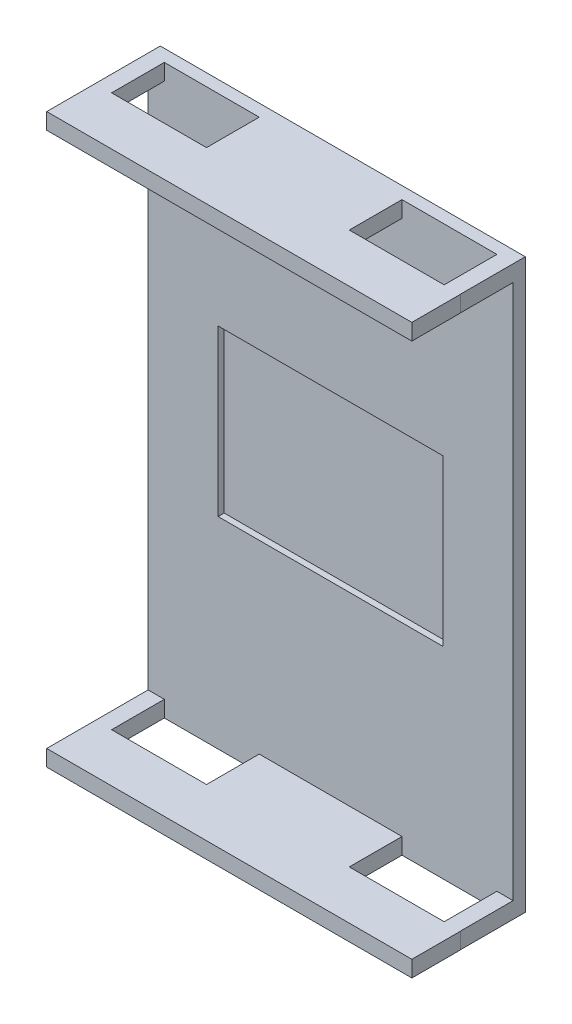
SolidWorks part; units mm, degrees
ref_plane "Front Plane" through (0, 0, 0) normal (1, 0, 0) x (0, 1, 0)
ref_plane "Top Plane" through (0, 0, 0) normal (0, 0, 1) x (0, 1, 0)
ref_plane "Right Plane" through (0, 0, 0) normal (0, 1, 0) x (-1, 0, 0)
sketch "Sketch1" plane through (0, 0, 0) normal (0, 0, 1) x (0, 1, 0)
  line L0 (-70, -45) -> (70, 45) construction
  line L1 (70, -45) -> (-70, -45)
  line L2 (70, -45) -> (70, 45)
  line L3 (70, 45) -> (-70, 45)
  line L4 (-70, -45) -> (-70, 45)
  line L5 (-70, 45) -> (70, -45) construction
  point P4 (0, 0)
  dimension "D1" = 90
  dimension "D2" = 140
extrude "Boss-Extrude1" add sketch "Sketch1" along normal blind 3
sketch "Sketch2" plane through (0, 0, 3) normal (0, 0, 1) x (1, 0, 0)
  line L0 (0, 70) -> (0, -70) construction
  line L1 (-45, 70) -> (-41, 70)
  line L2 (-45, 70) -> (-45, 66)
  line L3 (-45, 66) -> (-41, 66)
  line L4 (-41, 70) -> (-41, 66)
  line L5 (45, 70) -> (-45, 70) construction
  line L6 (-45, -70) -> (45, -70) construction
  line L7 (-45, 0) -> (45, 0) construction
  line L8 (-45, 70) -> (-45, -70) construction
  line L9 (45, -70) -> (45, 70) construction
  line L10 (45, 66) -> (41, 66)
  line L11 (41, 70) -> (41, 66)
  line L12 (45, 70) -> (41, 70)
  line L13 (45, 70) -> (45, 66)
  line L14 (45, -70) -> (45, -66)
  line L15 (45, -70) -> (41, -70)
  line L16 (41, -70) -> (41, -66)
  line L17 (45, -66) -> (41, -66)
  line L18 (-45, -66) -> (-41, -66)
  line L19 (-41, -70) -> (-41, -66)
  line L20 (-45, -70) -> (-41, -70)
  line L21 (-45, -70) -> (-45, -66)
  line L22 (-17.6, 70) -> (-13.6, 70)
  line L23 (-17.6, 70) -> (-17.6, 66)
  line L24 (-17.6, 66) -> (-13.6, 66)
  line L25 (-13.6, 70) -> (-13.6, 66)
  line L26 (17.6, 70) -> (17.6, 66)
  line L27 (17.6, 66) -> (13.6, 66)
  line L28 (13.6, 70) -> (13.6, 66)
  line L29 (17.6, 70) -> (13.6, 70)
  line L30 (17.6, -70) -> (13.6, -70)
  line L31 (13.6, -70) -> (13.6, -66)
  line L32 (17.6, -66) -> (13.6, -66)
  line L33 (17.6, -70) -> (17.6, -66)
  line L34 (-17.6, -70) -> (-17.6, -66)
  line L35 (-17.6, -66) -> (-13.6, -66)
  line L36 (-13.6, -70) -> (-13.6, -66)
  line L37 (-17.6, -70) -> (-13.6, -70)
  line L38 (-13.6, -66) -> (13.6, -66)
  line L39 (-13.6, -66) -> (-13.6, -70)
  line L40 (13.6, -66) -> (13.6, -70)
  line L41 (-13.6, -70) -> (13.6, -70)
  line L42 (-13.6, 66) -> (-13.6, 70)
  line L43 (-13.6, 66) -> (13.6, 66)
  line L44 (-13.6, 70) -> (13.6, 70)
  line L45 (13.6, 66) -> (13.6, 70)
  line M15 (45, 70) -> (-45, 70)
  line M16 (-45, 70) -> (-45, -70)
  line M17 (-45, -70) -> (45, -70)
  line M18 (45, -70) -> (45, 70)
  dimension "D1" = 4
  dimension "D2" = 4
  dimension "D3" = 23.4
extrude "Boss-Extrude2" add sketch "Sketch2" along normal blind 25 contours L4 L3 M15 M16 | L25 L23 L24 M15 | L28 L27 L26 M15 | L11 L10 M15 M18 | L19 L18 M17 M16 | L36 L35 L34 M17 | L25 L43 L28 M15 | L38 L36 L31 M17 | L32 L31 L30 L33 | L15 L16 L17 L14 region at (-43, 68, 3) region at (-15.6, 68, 3) region at (-43, -68, 3) region at (0, 68, 3) region at (15.6, 68, 3) region at (-15.6, -68, 3) region at (43, 68, 3) region at (0, -68, 3)
sketch "Sketch4" plane through (0, 0, 3) normal (0, 0, 1) x (1, 0, 0)
  line L0 (-27.75, -20.35) -> (27.75, -20.35)
  line L1 (-27.75, -20.35) -> (-27.75, 20.35)
  line L2 (27.75, -20.35) -> (27.75, 20.35)
  line L3 (-27.75, 20.35) -> (27.75, 20.35)
  line L4 (-27.75, -20.35) -> (27.75, 20.35) construction
  line L5 (27.75, -20.35) -> (-27.75, 20.35) construction
  point P1 (0, 0)
  dimension "D1" = 55.5
  dimension "D2" = 40.7
extrude "Cut-Extrude1" cut sketch "Sketch4" against normal blind 1.5
sketch "Sketch5" plane through (0, 0, 28) normal (0, 0, 1) x (1, 0, 0)
  line L0 (-45, -66) -> (-45, -70)
  line L1 (-45, -66) -> (45.0343, -66)
  line L2 (-45, -70) -> (45.0343, -70)
  line L3 (45.0343, -66) -> (45.0343, -70)
  line L4 (-45, 70) -> (-45, 66)
  line L5 (-45, 70) -> (45.0274, 70)
  line L6 (-45, 66) -> (45.0274, 66)
  line L7 (45.0274, 70) -> (45.0274, 66)
extrude "Boss-Extrude3" add sketch "Sketch5" against normal offset from surface (12 mm away) 13 up to face at (0, 0, 3)
